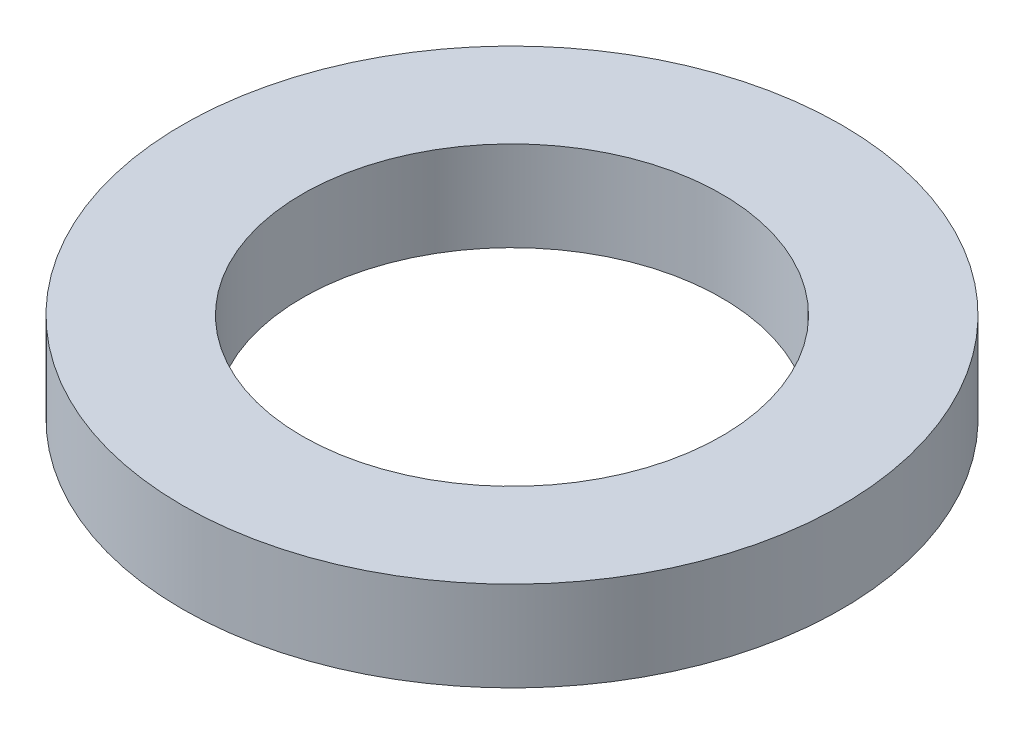
SolidWorks part; units mm, degrees
ref_plane "Front Plane" through (0, 0, 0) normal (0, 0, 1) x (1, 0, 0)
ref_plane "Top Plane" through (0, 0, 0) normal (0, 1, 0) x (1, 0, 0)
ref_plane "Right Plane" through (0, 0, 0) normal (1, 0, 0) x (0, 0, -1)
sketch "Sketch1" plane through (0, 0, 0) normal (0, 1, 0) x (1, 0, 0)
  circle A0 centre (0, 0) radius 55
  dimension "FLANGE_OD" = 110
extrude "Boss-Extrude1" add sketch "Sketch1" along normal blind 15
sketch "Sketch2" plane through (0, 0, 0) normal (0, 1, 0) x (1, 0, 0)
  circle A0 centre (0, 0) radius 35
  dimension "BORE_D" = 70
extrude "Cut-Extrude1" cut sketch "Sketch2" along normal through all
sketch "Sketch3" plane through (0, 15, 0) normal (0, 1, 0) x (1, 0, 0)
  circle A0 centre (0, 0) radius 22.434 construction
  circle A1 centre (-22.434, 0) radius 3.3319
  dimension "BOLT_D" = 6.6638
  dimension "BOLT_PCD" = 44.8681
extrude "Cut-Extrude2" cut sketch "Sketch3" against normal blind 12.7175 rebuild error yes
pattern_circular "CirPattern1" count 4 over 360 rebuild error yes
